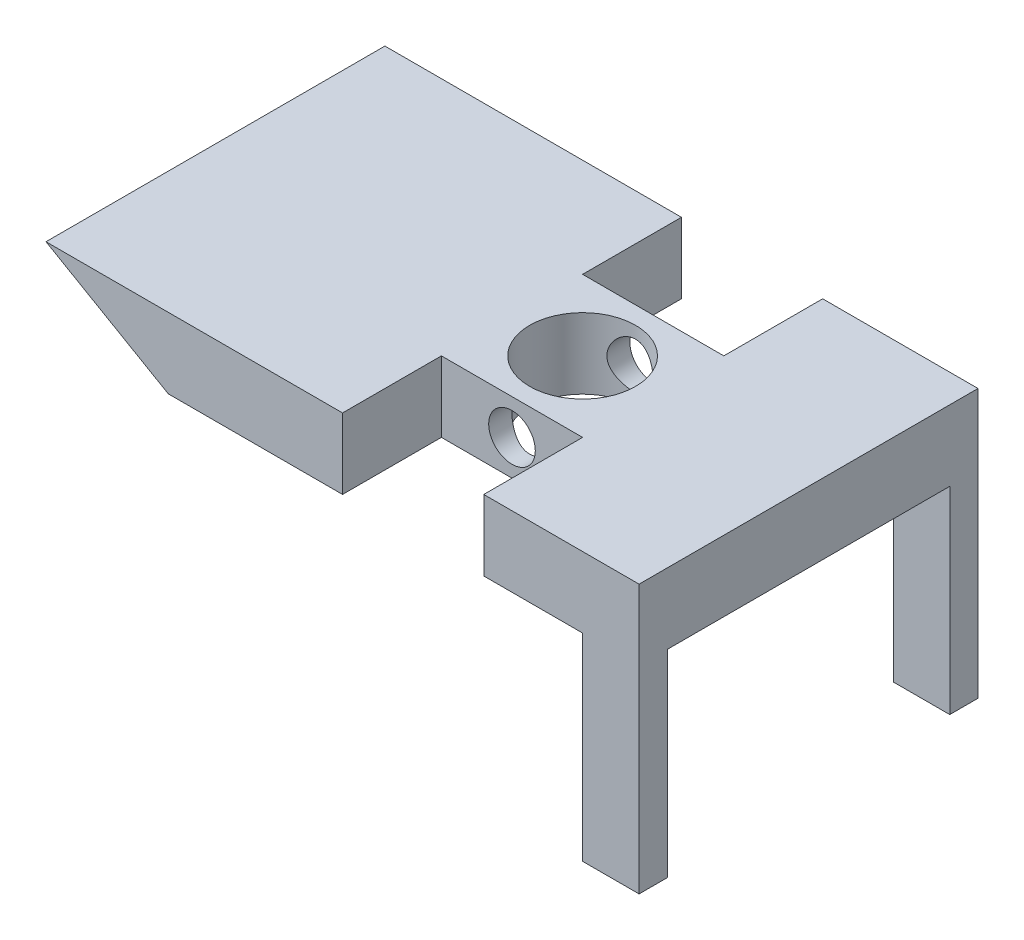
SolidWorks part; units mm, degrees
ref_plane "Front Plane" through (0, 0, 0) normal (0, 0, 1) x (1, 0, 0)
ref_plane "Top Plane" through (0, 0, 0) normal (0, 1, 0) x (1, 0, 0)
ref_plane "Right Plane" through (0, 0, 0) normal (1, 0, 0) x (0, 0, -1)
sketch "Sketch3" plane through (0, 0, 0) normal (0, 0, 1) x (1, 0, 0)
  line L0 (-21, 2.5) -> (-12.3397, -2.5)
  line L1 (-12.3397, -2.5) -> (21, -2.5)
  line L3 (-21, 2.5) -> (21, 2.5)
  line L4 (21, -2.5) -> (21, 2.5)
  line L5 (-13.8202, -1.6453) -> (21, 2.5) construction
  line L6 (-21, 2.5) -> (21, -2.5) construction
  arc A0 (-21, 2.5) -> (-12.3397, -2.5) centre (-22.4997, -10.0976) cw construction
  point P0 (0, 0)
  point P6 (0, 2.5)
  dimension "D1" = 42
  dimension "D2" = 150
  dimension "D4" = 5
extrude "Boss-Extrude1" add sketch "Sketch3" along normal mid plane 24
sketch "Sketch4" plane through (0, 0, 12) normal (0, 0, 1) x (1, 0, 0)
  line L0 (21, -2.5) -> (21, 2.5) construction
  line L1 (21, 2.5) -> (-21, 2.5) construction
  line L2 (10, -2.5) -> (0, -2.5)
  line L3 (10, -2.5) -> (10, 2.5)
  line L4 (10, 2.5) -> (0, 2.5)
  line L5 (0, -2.5) -> (0, 2.5)
  line L6 (10, -2.5) -> (0, 2.5) construction
  line L7 (10, 2.5) -> (0, -2.5) construction
  circle A2 centre (5, 0) radius 1.65
  dimension "D1" = 3.3
  dimension "D2" = 5
  dimension "D5" = 16
extrude "Cut-Extrude1" cut sketch "Sketch4" against normal up to next contours A2 region at (5, 0, 12)
extrude "Cut-Extrude3" cut sketch "Sketch4<3>" against normal blind 7
sketch "Sketch4<3>" plane through (0, 0, 12) normal (0, 0, 1) x (1, 0, 0) same geometry as "Sketch4"
mirror "Mirror1" about plane through (0, 0, 0) normal (0, 0, 1) of "Cut-Extrude3"
sketch "Sketch5" plane through (0, 2.5, 0) normal (0, 1, 0) x (1, 0, 0)
  line L0 (21, -12) -> (21, 12) construction
  circle A0 centre (5, 0) radius 3.75
  point P7 (21, 0)
  dimension "D2" = 7.5
  dimension "D1" = 16
extrude "Cut-Extrude2" cut sketch "Sketch5" against normal up to next
sketch "Sketch6" plane through (0, 0, 12) normal (0, 0, 1) x (1, 0, 0)
  line L0 (21, -2.5) -> (21, -16.5)
  line L1 (21, -16.5) -> (17, -16.5)
  line L2 (17, -16.5) -> (17, -2.5)
  line L3 (-12.3397, -2.5) -> (0, -2.5) construction
  line L4 (17, -2.5) -> (21, -2.5)
  dimension "D1" = 14
  dimension "D2" = 4
extrude "Boss-Extrude2" add sketch "Sketch6" against normal up to surface (24 mm away) up to face at (-8.3349, 0, -12)
sketch "Sketch7" plane through (21, 0, 0) normal (1, 0, 0) x (0, 0, -1)
  line L0 (12, -16.5) -> (-12, -16.5) construction
  line L1 (-10, -16.5) -> (10, -16.5)
  line L2 (-10, -16.5) -> (-10, -2.5)
  line L3 (-10, -2.5) -> (10, -2.5)
  line L4 (10, -16.5) -> (10, -2.5)
  point P6 (0, -2.5)
  dimension "D1" = 2
extrude "Cut-Extrude4" cut sketch "Sketch7" against normal blind 10
